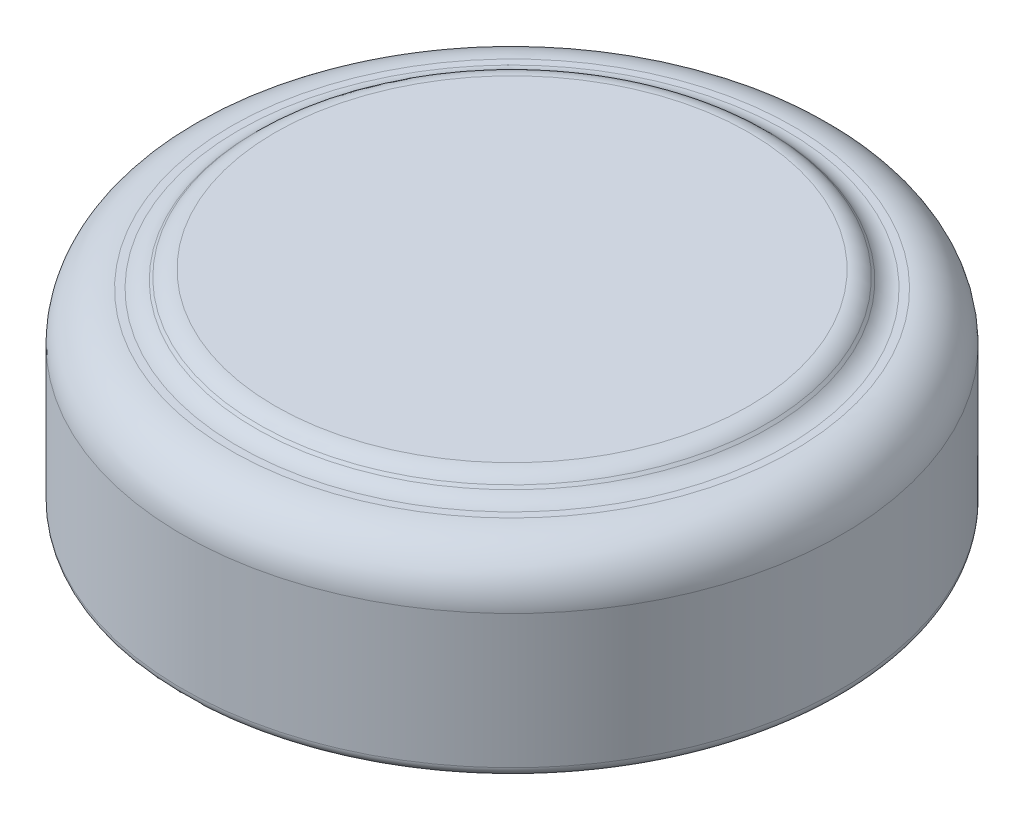
SolidWorks part; units mm, degrees
ref_plane "Front Plane" through (0, 0, 0) normal (0, 0, 1) x (1, 0, 0)
ref_plane "Top Plane" through (0, 0, 0) normal (0, 1, 0) x (1, 0, 0)
ref_plane "Right Plane" through (0, 0, 0) normal (1, 0, 0) x (0, 0, -1)
sketch "Sketch1" plane through (0, 0, 0) normal (0, 0, 1) x (1, 0, 0)
  line L0 (0, 0) -> (-3.3, 0)
  line L1 (-3.4, 0.1) -> (-3.4, 1.478)
  line L2 (-2.4444, 2.15) -> (0, 2.15)
  line L3 (0, 2.15) -> (0, 0)
  line L4 (-2.6212, 2.0768) -> (-2.6468, 2.0512)
  line L7 (-2.9, 1.978) -> (-2.8236, 1.978)
  arc A0 (-3.4, 1.478) -> (-2.9, 1.978) centre (-2.9, 1.478) cw
  arc A1 (-2.8236, 1.978) -> (-2.6468, 2.0512) centre (-2.8236, 2.228) ccw
  arc A2 (-2.4444, 2.15) -> (-2.6212, 2.0768) centre (-2.4444, 1.9) ccw
  arc A3 (-3.3, 0) -> (-3.4, 0.1) centre (-3.3, 0.1) cw
  point P9 (-3.4, 1.978)
  point P12 (-2.72, 1.978)
  point P13 (-2.72, 1.978)
  point P14 (-2.548, 2.15)
  point P17 (-3.4, 0)
  dimension "D6" = 0.5
  dimension "D7" = 0.25
  dimension "D8" = 0.1
  dimension "D1" = 3.4
  dimension "D2" = 2.15
  dimension "D3" = 2.72
  dimension "D4" = 1.978
  dimension "D5" = 45
revolve "Revolve1" add sketch "Sketch1" angle 360 about L3
sketch "Sketch2" plane through (0, 0, 0) normal (0, -1, 0) x (1, 0, 0)
  line L0 (0.25, 0.25) -> (1.5, 0.25)
  line L1 (-0.25, 1.5) -> (0.25, 1.5)
  line L2 (-0.25, 1.5) -> (-0.25, 0.25)
  line L3 (-0.25, -1.5) -> (0.25, -1.5)
  line L4 (0.25, 1.5) -> (0.25, 0.25)
  line L5 (-1.5, 0.25) -> (-0.25, 0.25)
  line L6 (-1.5, 0.25) -> (-1.5, -0.25)
  line L7 (-1.5, -0.25) -> (-0.25, -0.25)
  line L8 (1.5, 0.25) -> (1.5, -0.25)
  line L9 (0.25, -0.25) -> (1.5, -0.25)
  line L10 (-0.25, -0.25) -> (-0.25, -1.5)
  line L11 (0.25, -0.25) -> (0.25, -1.5)
  circle A0 centre (0, 0) radius 2 construction
  text T0 "                SR60" font "Century Gothic" height 1
  dimension "D1" = 4
  dimension "D2" = 3
  dimension "D3" = 3
  dimension "D4" = 0.5
  dimension "D5" = 0.5
  dimension "D6" = 0.25
  dimension "D7" = 0.25
  dimension "D8" = 1.5
  dimension "D9" = 1.5
wrap "Wrap1" sketch "Sketch2" wrap type scribe source sketch "Sketch2" face at (-3.3, 0, 0)
